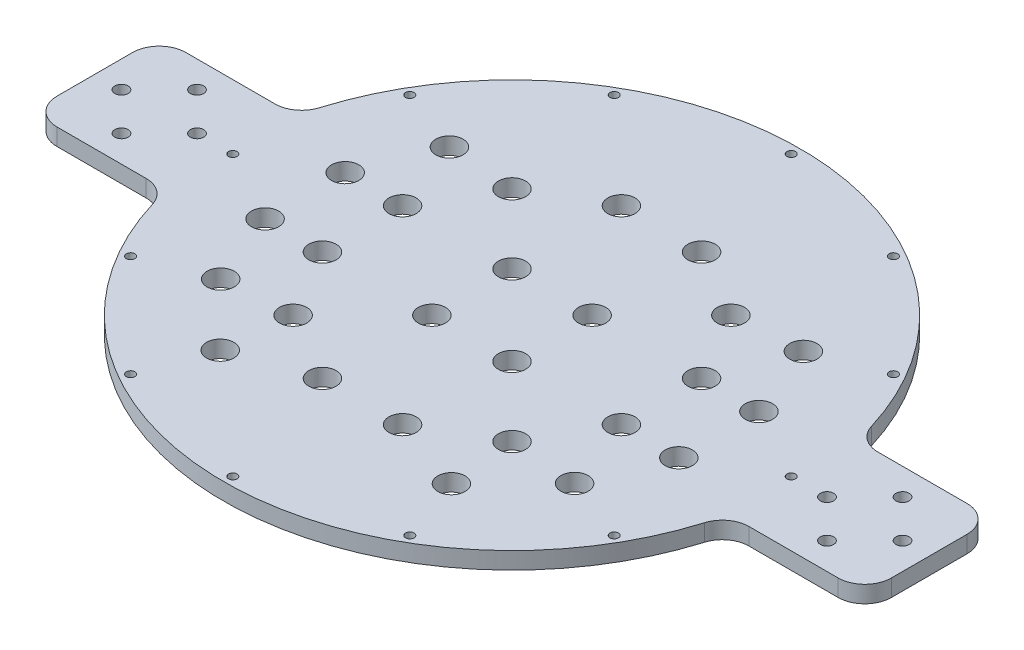
SolidWorks part; units mm, degrees
material "AISI 304"
ref_plane "Front Plane" through (0, 0, 0) normal (0, 0, 1) x (1, 0, 0)
ref_plane "Top Plane" through (0, 0, 0) normal (0, 1, 0) x (1, 0, 0)
ref_plane "Right Plane" through (0, 0, 0) normal (1, 0, 0) x (0, 0, -1)
sketch "Sketch1" plane through (0, 0, 0) normal (0, 1, 0) x (1, 0, 0)
  circle A1 centre (0, 0) radius 107.95
  dimension "D2" = 215.9
extrude "Boss-Extrude1" add sketch "Sketch1" along normal blind 6.35
hole_wizard "M3 Clearance Hole1" positions "Sketch9" profile "Sketch10" hole size "M3" standard "ANSI Metric" end condition through all
sketch "Sketch9" plane through (0, 6.35, 0) normal (0, 1, 0) x (1, 0, 0)
  line L0 (0, 0) -> (0, 104.55) construction
  point P2 (0, 104.55)
  dimension "D1" = 104.55
sketch "Sketch10" plane through (0, 6.35, -104.55) normal (1, 0, 0) x (0, 0, 1)
  line L0 (0, 0) -> (0, 6.35)
  line L1 (0, 6.35) -> (1.6, 6.35)
  line L2 (1.6, 6.35) -> (1.6, 0)
  line L5 (1.6, 0) -> (0, 0)
  line L11 (0, -6.35) -> (0, 107.95) construction
  dimension "Thru Hole Dia." = 3.2
  dimension "Thru Hole Depth" = 6.35
pattern_circular "CirPattern1" count 12 over 360 about axis through (0, 6.35, 0) along (0, -1, 0) of "M3 Clearance Hole1" reverse direction yes
sketch "Sketch2" plane through (0, 0, 0) normal (0, 1, 0) x (1, 0, 0)
  line L0 (-156.2343, 24.1421) -> (-105.2158, 24.1421)
  line L1 (-105.2158, -24.1421) -> (-156.2343, -24.1421)
  line L2 (-156.2343, -24.1421) -> (-156.2343, 24.1421)
  line L3 (-156.2343, 0) -> (0, 0) construction
  line L4 (-146.2343, 0) -> (-132.0921, 14.1421) construction
  line L5 (-132.0921, 14.1421) -> (-117.95, 0) construction
  line L6 (-117.95, 0) -> (-132.0921, -14.1421) construction
  line L7 (-132.0921, -14.1421) -> (-146.2343, 0) construction
  circle A0 centre (0, 0) radius 107.95 construction
  circle A1 centre (0, 0) radius 107.95 construction
  arc A2 (-105.2158, 24.1421) -> (-105.2158, -24.1421) centre (0, 0) ccw
  point P11 (-107.95, 0)
  dimension "D1" = 20
  dimension "D2" = 10
  dimension "D3" = 10
  dimension "D4" = 10
extrude "Boss-Extrude2" add sketch "Sketch2" along normal up to surface (6.35 mm away) up to face at (52.275, 6.35, -88.943)
fillet "Fillet1" radius 10 4 edges at (-105.2158, 3.175, -24.1421) (-156.2343, 3.175, -24.1421) (-156.2343, 3.175, 24.1421) (-105.2158, 3.175, 24.1421)
mirror "Mirror1" about plane through (0, 0, 0) normal (1, 0, 0) of "Boss-Extrude2", "Fillet1"
hole_wizard "#10 Clearance Hole3" positions "Sketch7" profile "Sketch8" hole size "#10" standard "ANSI Inch" end condition through all
sketch "Sketch7" plane through (0, 6.35, 0) normal (0, 1, 0) x (1, 0, 0)
  line L0 (-117.95, 0) -> (-132.0921, -14.1421) construction
  line L1 (-132.0921, -14.1421) -> (-146.2343, 0) construction
  line L2 (-146.2343, 0) -> (-132.0921, 14.1421) construction
  line L3 (-132.0921, 14.1421) -> (-117.95, 0) construction
  line L4 (-117.95, 0) -> (-132.0921, -14.1421) construction
  line L5 (-132.0921, -14.1421) -> (-146.2343, 0) construction
  line L6 (-146.2343, 0) -> (-132.0921, 14.1421) construction
  line L7 (-132.0921, 14.1421) -> (-117.95, 0) construction
  line L8 (0, 107.95) -> (0, -107.95) construction
  line L10 (132.0921, 14.1421) -> (117.95, 0) construction
  line L11 (146.2343, 0) -> (132.0921, 14.1421) construction
  line L12 (132.0921, -14.1421) -> (146.2343, 0) construction
  line L13 (117.95, 0) -> (132.0921, -14.1421) construction
  arc A0 (103.3286, 31.2475) -> (-103.3286, 31.2475) centre (0, 0) ccw construction
  arc A1 (-103.3286, -31.2475) -> (103.3286, -31.2475) centre (0, 0) ccw construction
  point P0 (-132.0921, -14.1421)
  point P2 (-117.95, 0)
  point P4 (-132.0921, 14.1421)
  point P6 (-146.2343, 0)
  point P29 (146.2343, 0)
  point P30 (132.0921, 14.1421)
  point P31 (117.95, 0)
  point P32 (132.0921, -14.1421)
sketch "Sketch8" plane through (-132.0921, 6.35, 14.1421) normal (1, 0, 0) x (0, 0, 1)
  line L0 (0, 0) -> (0, 6.35)
  line L1 (0, 6.35) -> (2.4892, 6.35)
  line L2 (2.4892, 6.35) -> (2.4892, 0)
  line L5 (2.4892, 0) -> (0, 0)
  line L11 (0, -6.35) -> (0, 107.95) construction
  dimension "Thru Hole Dia." = 4.9784
  dimension "Thru Hole Depth" = 6.35
sketch "Sketch11" plane through (0, 6.35, 0) normal (0, 1, 0) x (1, 0, 0)
  line L0 (-88.9, 0) -> (0, 0) construction
  line L1 (0, 0) -> (0, 88.9) construction
  circle A0 centre (0, 0) radius 88.9 construction
  circle A1 centre (-66.2622, 42.8314) radius 5.1
  circle A2 centre (-77.461, 15) radius 5.1
  circle A3 centre (-77.461, -15) radius 5.1
  circle A4 centre (-66.2622, -42.8314) radius 5.1
  circle A9 centre (15, 15) radius 5.1
  circle A10 centre (-15, 15) radius 5.1
  circle A12 centre (-15, -15) radius 5.1
  circle A14 centre (-55.9808, -15) radius 5.1
  circle A15 centre (-40.9808, -40.9808) radius 5.1
  circle A16 centre (-15, -55.9808) radius 5.1
  circle A17 centre (15, -55.9808) radius 5.1
  circle A18 centre (-55.9808, 15) radius 5.1
  circle A20 centre (55.9808, -15) radius 5.1
  circle A21 centre (40.9808, -40.9808) radius 5.1
  circle A26 centre (0, 0) radius 21.2132 construction
  arc A27 (-64.809, 45) -> (-64.809, -45) centre (0, 0) ccw construction
  circle A28 centre (66.2622, -42.8314) radius 5.1
  circle A29 centre (77.461, -15) radius 5.1
  circle A30 centre (77.461, 15) radius 5.1
  circle A31 centre (66.2622, 42.8314) radius 5.1
  circle A32 centre (0, 0) radius 57.9555 construction
  circle A33 centre (55.9808, 15) radius 5.1
  circle A34 centre (40.9808, 40.9808) radius 5.1
  circle A35 centre (15, 55.9808) radius 5.1
  circle A36 centre (-15, 55.9808) radius 5.1
  circle A37 centre (-40.9808, 40.9808) radius 5.1
  circle A38 centre (15, -15) radius 5.1
  circle A39 centre (-43.2905, -65.9632) radius 5.1
  circle A40 centre (43.2905, -65.9632) radius 5.1
  point P57 (0, 0)
  point P58 (0, 0)
  point P59 (0, 0)
  dimension "D1" = 177.8
  dimension "D2" = 10.2
  dimension "D3" = 30
  dimension "D8" = 10
  dimension "D9" = 90
  dimension "D11" = 30
  dimension "D4" = 30
  dimension "D5" = 30
  dimension "D6" = 30
  dimension "D7" = 30
  dimension "D10" = 30
  dimension "D12" = 30
  dimension "D13" = 30
  dimension "D14" = 30
  dimension "D15" = 30
  dimension "D16" = 30
  dimension "D17" = 30
  dimension "D18" = 30
  dimension "D19" = 30
  dimension "D20" = 30
extrude "Cut-Extrude1" cut sketch "Sketch11" against normal up to next (6.35 mm away)
